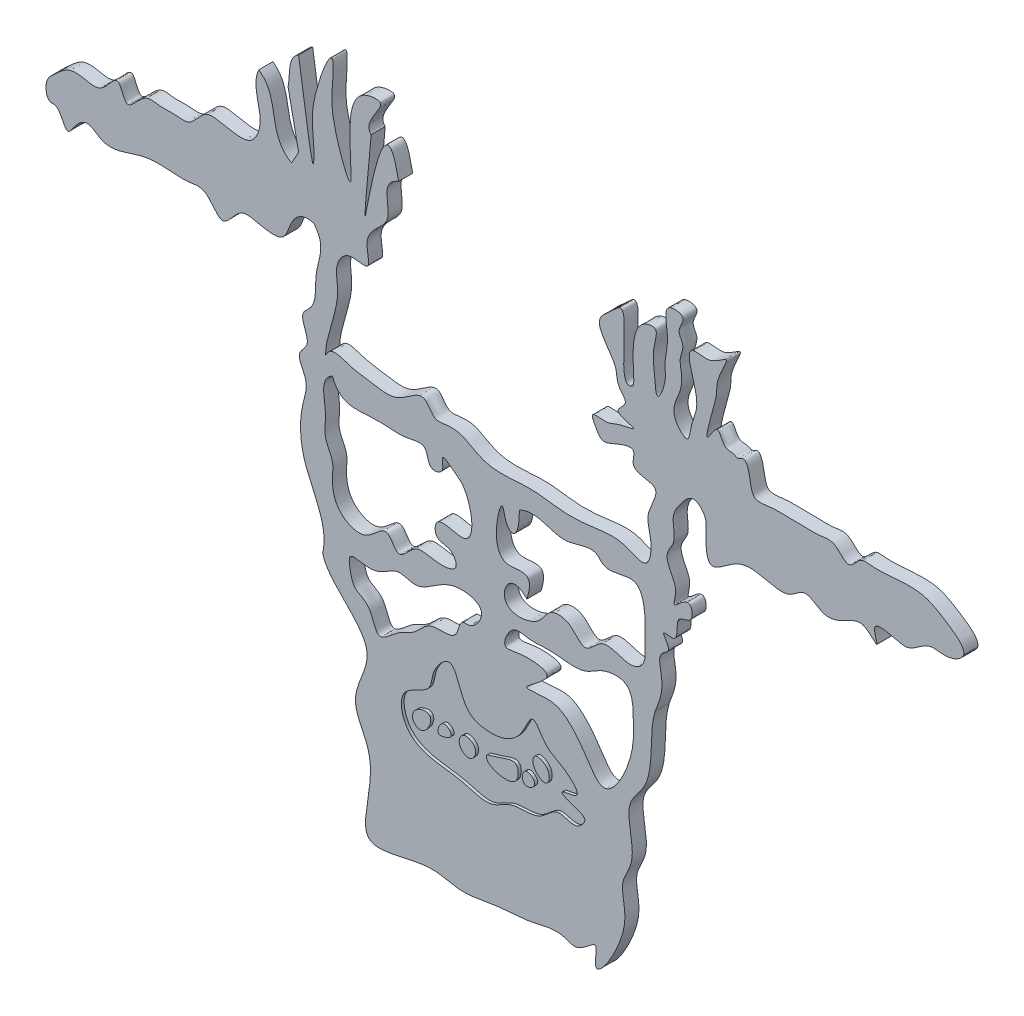
SolidWorks part; units mm, degrees
ref_plane "Plan de face" through (0, 0, 0) normal (0, 0, 1) x (1, 0, 0)
ref_plane "Plan de dessus" through (0, 0, 0) normal (0, 1, 0) x (1, 0, 0)
ref_plane "Plan de droite" through (0, 0, 0) normal (1, 0, 0) x (0, 0, -1)
sketch "Esquisse5" plane through (0, 0, 0) normal (0, 0, 1) x (1, 0, 0)
  spline S0 degree 3 poles (-109.3445, 25.1534) (-107.5893, 29.4219) (-101.3392, 25.9029) (-92.6956, 25.3142) (-83.4645, 22.6763) (-74.413, 33.2755) (-71.2749, 24.7007) (-66.4529, 25.3335) (-60.8204, 25.8472) (-54.3045, 20.5029) (-45.153, 19.8653) (-34.9131, 21.2066) (-24.0216, 18.622) (-12.6516, 20.1709) (-3.8665, 21.2156) (5.3646, 15.6477) (7.1198, 26.6974) (3.2173, 33.4052) (11.7792, 45.093) (-1.969, 43.5994) (1.4376, 52.0963) (-6.02, 50.089) (-11.0528, 46.8236) (-13.4058, 51.1132) (-15.6993, 55.6454) (-8.9166, 53.9478) (-5.9802, 56.3886) (4.108, 57.5122) (-8.7508, 59.2174) (-0.962, 63.8466) (-6.0647, 67.643) (-5.6768, 73.3095) (-9.5713, 78.0773) (-13.8345, 85.1581) (-8.5077, 88.8259) (0.4502, 98.2004) (-6.9651, 65.1054) (0, 70.636) knots 0 0 0 0 0.038716 0.066818 0.105889 0.146717 0.169739 0.177879 0.20067 0.234895 0.269429 0.30528 0.355982 0.398433 0.437537 0.464385 0.493232 0.529195 0.564337 0.596403 0.612682 0.632285 0.657558 0.673837 0.684133 0.703736 0.721045 0.742877 0.766185 0.783794 0.800555 0.820691 0.846941 0.873241 0.900963 0.913678 1 1 1 1
  spline S1 degree 3 poles (0, 70.636) (0.8053, 74.1338) (-3.1075, 91.5186) (8.9993, 92.506) (6.4299, 84.3585) (7.424, 80.3323) (8.0477, 68.4861) (11.9386, 77.7085) (10.6243, 83.9209) (13.2943, 91.2366) (9.6941, 102.3641) (19.6931, 100.9769) (14.8522, 95.7025) (18.5565, 91.734) (15.9877, 87.3637) (17.3791, 82.5577) (16.9196, 75.8625) (11.9734, 69.6035) (19.5998, 61.6604) (20.5501, 70.6781) (25.1421, 76.9754) (16.8283, 92.3811) (24.2143, 92.0829) (27.8296, 91.1829) (35.8211, 98.2302) (29.3274, 88.1257) (29.7364, 82.4119) (28.1594, 77.4041) (24.3037, 62.9473) (30.2481, 74.9158) (31.4808, 68.5753) (33.9084, 67.3915) (35.4935, 67.7493) (37.0636, 66.3876) (39.8623, 69.0192) (41.6497, 62.3983) (42.1041, 56.2374) (49.6882, 58.0085) (55.4741, 57.4372) (61.145, 57.6949) (66.2026, 57.3374) (71.7205, 59.0931) (76.5046, 50.82) (80.002, 58.066) (85.2929, 57.3078) (92.1595, 57.5578) (102.1598, 58.778) (110.3187, 54.2176) (120.723, 47.0205) (111.4915, 41.8788) (104.4068, 44.6031) (98.8248, 37.9068) (92.5887, 39.2631) (83.4924, 41.6725) (88.1798, 31.3671) (82.2057, 38.9151) (75.7762, 36.6539) (68.6206, 31.605) (61.0853, 39.3937) (55.3505, 32.6841) (46.6559, 34.4895) (37.2691, 36.8871) (25.9593, 24.6172) (25.5554, 37.3297) (26.158, 43.1802) (21.1466, 48.0577) (16.562, 42.6011) (12.9148, 37.0996) (15.6812, 30.0513) (10.4935, 24.536) (13.9024, 18.9519) (15.4944, 14.849) (13.2213, 7.817) (20.25, 16.8547) (21.7448, 7.3304) (13.6535, 8.3206) (17.1663, -1.6092) (8.5371, 1.2339) (14.2305, -4.4779) (8.0837, -7.0098) (11.3423, -16.1767) (9.4066, -21.6006) (7.7197, -25.6917) knots 0 0 0 0 0.045125 0.049215 0.059033 0.077849 0.089591 0.101354 0.11284 0.130913 0.149078 0.157421 0.167541 0.174531 0.184484 0.192706 0.203372 0.223278 0.234285 0.242046 0.262102 0.290783 0.294055 0.302236 0.314316 0.330881 0.339103 0.350018 0.368971 0.378972 0.388474 0.390275 0.394745 0.397177 0.400956 0.411147 0.422653 0.434106 0.447196 0.459468 0.466831 0.477466 0.490402 0.502673 0.506764 0.520672 0.544397 0.561597 0.5813 0.593788 0.606878 0.623723 0.633575 0.647507 0.656654 0.667781 0.676003 0.696456 0.711497 0.722862 0.738406 0.759677 0.780901 0.799195 0.808231 0.818403 0.829191 0.841996 0.85754 0.866687 0.881184 0.888727 0.896135 0.907501 0.916647 0.925794 0.939899 0.946444 0.955636 0.961421 0.97617 1 1 1 1
  spline S2 degree 3 poles (7.7197, -25.6917) (5.86, -31.6938) (7.081, -40.4964) (4.1065, -51.8144) (-2.5229, -57.9761) (-0.9213, -67.6544) (0.3405, -76.191) (-6.0452, -85.948) (1.4123, -96.2082) (-15.6555, -122.9421) (-12.0341, -104.6237) (-19.2372, -113.8384) (-26.9783, -109.4812) (-35.9985, -113.1217) (-48.753, -113.0684) (-60.3803, -116.5393) (-75.2312, -111.4227) (-96.823, -122.2835) (-94.0713, -101.5301) (-91.8687, -89.1125) (-102.2594, -74.62) (-86.759, -54.7603) (-108.1357, -44.5783) (-110.3558, -36.0857) knots 0 0 0 0 0.069204 0.098549 0.128834 0.163224 0.200739 0.224549 0.282385 0.351324 0.371645 0.400341 0.416282 0.464966 0.499497 0.562335 0.592403 0.681558 0.715947 0.784726 0.829733 0.894184 1 1 1 1
  spline S3 degree 3 poles (-110.3558, -36.0857) (-108.0423, -26.3601) (-118.3266, -14.2726) (-118.7144, 3.6631) (-114.8605, 14.2325) (-120.5579, 20.8624) (-113.3368, 26.0818) (-119.7152, 33.3225) (-111.9733, 38.7318) (-114.3277, 50.5388) (-108.8733, 58.305) (-113.5021, 63.8189) knots 0 0 0 0 0.256249 0.424787 0.497442 0.568529 0.611922 0.700995 0.737981 0.848138 1 1 1 1
  spline S4 degree 3 poles (-113.5021, 63.8189) (-117.2169, 64.9742) (-121.7481, 61.6652) (-123.7192, 51.4764) (-132.7312, 54.0058) (-140.6598, 55.2619) (-145.9399, 43.7999) (-151.1861, 56.0157) (-157.6195, 54.0793) (-164.3136, 54.3377) (-172.456, 55.2282) (-180.8309, 51.617) (-188.4989, 50.4972) (-193.4763, 55.5367) (-197.9973, 52.3988) (-201.64, 45.1731) (-203.3779, 54.6671) (-208.498, 53.929) (-209.2844, 60.5865) (-204.9438, 64.0796) (-200.8354, 68.1395) (-194.8236, 67.6944) (-188.3993, 65.5013) (-182.827, 76.7366) (-180.0769, 63.0752) (-174.2837, 74.1888) (-167.7841, 72.1256) (-163.064, 72.8538) (-156.393, 71.546) (-153.1821, 79.3156) (-144.5205, 78.1574) (-135.5079, 75.4657) (-130.4643, 88.4219) (-135.7655, 95.1484) (-133.0428, 101.2372) knots 0 0 0 0 0.042216 0.071541 0.118379 0.137114 0.178374 0.218206 0.244435 0.259423 0.310009 0.350927 0.382777 0.407913 0.429762 0.449677 0.484223 0.48797 0.515249 0.536611 0.566234 0.586842 0.614945 0.650934 0.676962 0.715948 0.73843 0.762786 0.781521 0.822781 0.84339 0.893975 0.924987 1 1 1 1
  spline S5 degree 3 poles (-133.0428, 101.2372) (-124.9979, 95.6095) (-130.5426, 83.8627) (-121.4015, 78.3705) knots 0 0 0 0 1 1 1 1
  spline S6 degree 1 poles (-121.4015, 78.3705) (-118.907, 82.9438) knots 0 0 1 1
  spline S7 degree 3 poles (-118.907, 112.8785) (-123.089, 110.3691) (-121.7421, 105.1701) (-122.6488, 101.2372) knots 0 0 0 0 1 1 1 1
  spline S8 degree 1 poles (-122.6488, 101.2372) (-118.907, 82.9438) knots 0 0 1 1
  spline S9 degree 3 poles (-118.907, 112.8785) (-117.987, 108.8644) (-113.4179, 71.5109) (-113.4509, 91.3381) (-115.6714, 99.2659) (-105.9463, 124.8116) (-106.9005, 108.6073) (-107.7487, 99.3774) (-97.8361, 72.1229) (-102.3522, 100.9727) (-98.2312, 112.8578) (-85.4927, 113.5021) (-96.5783, 104.4145) (-93.1299, 101.2372) knots 0 0 0 0 0.203682 0.231519 0.326163 0.443507 0.493613 0.55207 0.681472 0.803953 0.895137 0.917406 1 1 1 1
  spline S10 degree 3 poles (-93.1299, 101.2372) (-99.727, 29.6469) (-90.5137, 130.523) (-83.3772, 91.7419) knots 0 0 0 0 1 1 1 1
  spline S11 degree 3 poles (-83.3772, 91.7419) (-90.4487, 89.0332) (-82.1452, 76.719) (-97.4311, 71.2785) (-92.0615, 57.9547) (-101.9759, 61.8394) (-106.261, 54.7014) (-103.357, 42.6183) (-109.2901, 32.7752) (-109.3445, 25.1534) knots 0 0 0 0 0.182686 0.350003 0.446213 0.524078 0.620688 0.69561 1 1 1 1
  spline S12 degree 3 poles (-106.85, 20.1643) (-104.4176, 13.083) (-96.6637, 14.4454) (-87.0757, 14.4695) (-81.1053, 13.6737) (-72.7921, 16.7083) (-73.1953, 8.2187) (-64.4991, 10.4032) (-71.1458, 18.672) (-61.948, 11.0176) knots 0 0 0 0 0.292957 0.410083 0.535017 0.659951 0.764711 0.829986 1 1 1 1
  spline S13 degree 3 poles (-61.948, 11.0176) (-58.0095, 8.5158) (-53.229, -12.6527) (-70.4415, -2.7478) (-70.6719, -12.2414) (-64.6769, -11.3045) (-61.2675, -18.2118) (-70.8685, -19.2053) (-77.5919, -16.0195) (-83.4796, -25.9551) (-87.6215, -14.8363) (-93.5991, -24.0033) (-100.9517, -23.2409) (-106.4949, -18.4186) (-107.1233, -11.8842) (-106.311, -5.4546) (-110.3923, -0.1476) (-108.2057, 9.249) (-111.8764, 17.3936) (-106.85, 20.1643) knots 0 0 0 0 0.141144 0.214347 0.246175 0.28755 0.319673 0.374752 0.435224 0.489982 0.532801 0.596765 0.64313 0.691472 0.753 0.784828 0.837727 0.890242 1 1 1 1
  spline S14 degree 3 poles (-37.834, -13.9279) (-34.3708, -3.014) (-45.4498, -10.1611) (-50.0257, 0.0267) (-46.6057, 14.1179) (-45.1788, 2.9802) (-40.4947, 1.6382) (-40.4757, 12.1082) knots 0 0 0 0 0.291808 0.452467 0.680923 0.763866 1 1 1 1
  spline S15 degree 3 poles (-40.4757, 12.1082) (-33.8644, 15.4003) (-26.4482, 7.1618) (-14.3964, 14.5729) (-9.7666, 8.4806) (-4.6314, 10.551) (3.2143, 11.0146) (4.4297, 0.9831) (3.9653, -6.4701) (4.6546, -13.3829) (-2.5433, -17.4116) (-10.3977, -10.522) (-17.3152, -21.6724) (-22.1852, -12.6994) (-30.3709, -12.9154) (-33.4257, -20.9458) (-50.3798, -22.2502) (-43.8265, -7.8239) (-37.834, -13.9279) knots 0 0 0 0 0.130404 0.212458 0.225808 0.291887 0.310767 0.396955 0.445727 0.503148 0.528517 0.613998 0.668135 0.726665 0.773865 0.820643 0.908748 1 1 1 1
  spline S16 degree 3 poles (-69.4252, -24.9578) (-62.0643, -21.5416) (-51.0142, -24.6948) (-56.5213, -32.8682) (-61.8953, -31.9406) (-62.0215, -40.6856) (-72.4837, -37.0863) (-77.1682, -44.7125) (-83.8695, -46.3481) (-91.4744, -55.1585) (-92.7397, -43.4929) (-99.5179, -41.6386) (-100.504, -36.8842) (-101.5507, -30.5349) (-93.3049, -33.4359) (-88.393, -30.8721) (-83.1039, -27.5261) (-76.6527, -30.7738) (-69.4252, -24.9578) (-62.0643, -21.5416) (-51.0142, -24.6948) knots -0.207888 -0.158201 -0.084774 0 0.058602 0.128869 0.139409 0.186335 0.264119 0.327318 0.383463 0.450039 0.522701 0.565587 0.610699 0.642319 0.6935 0.757509 0.792112 0.841799 0.915226 1 1.058602 1.128869 1.139409 only from (-60.285, -22.6588) to (-60.285, -22.6588)
  spline S17 degree 3 poles (-38.966, -31.3288) (-47.5023, -33.6205) (-43.5055, -24.106) (-36.488, -26.3957) (-28.3257, -24.9207) (-18.3312, -27.6817) (-11.1552, -21.6964) (-0.2181, -20.6913) (0.0231, -33.8116) (0.2507, -44.399) (-9.4883, -63.9536) (-17.2987, -50.5788) (-22.3616, -44.2959) (-28.8973, -39.837) (-43.4581, -43.2274) (-24.101, -32.293) (-38.966, -31.3288) (-47.5023, -33.6205) (-43.5055, -24.106) knots -0.168834 -0.101482 -0.025755 0 0.049951 0.081412 0.138616 0.224421 0.269573 0.329636 0.398438 0.478824 0.5988 0.659915 0.726618 0.773963 0.831166 0.898518 0.974245 1 1.049951 1.081412 1.138616 only from (-45.3177, -32.3438) to (-45.3177, -32.3438)
  point P114 (-59.3851, 13.9625)
  point P229 (-86.534, 92.0905)
  point P252 (-105.3667, 54.2565)
  point P266 (-105.0789, 48.4359)
  point P271 (21.4038, 46.3571)
  point P275 (-118.907, 63.0945)
  point P285 (-98.7145, -41.0748)
  point P293 (5.8507, -43.9851)
  point P297 (6.4346, -34.3001)
  point P301 (-5.3523, 56.0203)
  point P305 (26.5556, 68.0611)
  point P309 (36.479, 78.3705)
  point P313 (35.6605, 70.3118)
  point P317 (29.8293, 71.9487)
  point P320 (32.6937, 68.0611)
  point P322 (35.7628, 67.345)
  point P323 (36.8882, 66.8335)
  point P324 (33.5122, 67.6519)
  point P325 (41.2872, 63.0945)
  point P326 (0, 0)
  point P327 (0, 70.636)
  point P328 (8.6131, 71.6798)
  point P329 (11.1183, 77.1076)
  point P330 (-67.7687, 13.0964)
  point P331 (-61.948, 11.0176)
  point P332 (-68.1523, 10.2504)
  point P333 (-46.329, 10.0491)
  point P334 (-40.4757, 12.1082)
  point P335 (-44.2652, 4.5292)
extrude "Boss.-Extru.1" add sketch "Esquisse5" along normal blind 2.5 and the other way blind 2.5
sketch "Esquisse10" plane through (0, 0, 2.5) normal (0, 0, 1) x (1, 0, 0)
  spline S0 degree 3 poles (-71.7082, -52.1571) (-62.9184, -42.3492) (-61.5257, -59.1414) (-50.0357, -62.4875) (-40.1173, -60.0504) (-35.9862, -46.6642) (-30.851, -57.3509) (-25.4724, -57.9903) (-16.7592, -66.6161) (-27.3959, -66.2868) (-21.5637, -69.6638) (-15.27, -70.2684) (-20.6675, -76.6957) (-27.2468, -71.8114) (-33.3059, -80.7937) (-42.9312, -78.2809) (-50.9315, -85.1058) (-60.4431, -81.072) (-70.4795, -80.4944) (-81.4537, -77.1571) (-84.2609, -62.3207) (-71.4637, -60.6586) (-71.7082, -52.1571) (-62.9184, -42.3492) (-61.5257, -59.1414) knots -0.133763 -0.074366 -0.043498 0 0.074169 0.111193 0.189975 0.228193 0.264295 0.316051 0.351334 0.380169 0.395456 0.431496 0.454031 0.49032 0.533246 0.593544 0.633375 0.691239 0.744913 0.806538 0.866237 0.925634 0.956502 1 1.074169 1.111193 1.189975 only from (-65.5402, -47.1818) to (-65.5402, -47.1818)
extrude "Enlèv. mat.-Extru.1" cut sketch "Esquisse10" against normal blind 1 and the other way blind 1
sketch "Esquisse11" plane through (0, 0, 2.5) normal (0, 0, 1) x (1, 0, 0)
  spline S0 degree 3 poles (-69.7666, -65.9105) (-76.9585, -66.3187) (-79.4724, -70.8228) (-74.178, -74.9917) (-69.7666, -65.9105) (-76.9585, -66.3187) (-79.4724, -70.8228) knots -0.761015 -0.577137 -0.213754 0 0.238985 0.422863 0.786246 1 1.238985 1.422863 1.786246 only from (-76.2453, -66.9696) to (-76.2453, -66.9696)
  spline S1 degree 3 poles (-70.3204, -71.4831) (-66.6909, -70.9588) (-63.1967, -69.4779) (-67.9341, -64.9138) (-70.3204, -71.4831) (-66.6909, -70.9588) (-63.1967, -69.4779) knots -0.7463 -0.476415 -0.134358 0 0.2537 0.523585 0.865642 1 1.2537 1.523585 1.865642 only from (-67.2683, -70.9732) to (-67.2683, -70.9732)
  spline S2 degree 3 poles (-54.5085, -68.5066) (-60.0647, -65.6897) (-61.9721, -68.8905) (-61.5328, -71.7372) (-57.5478, -74.4569) (-54.5085, -68.5066) (-60.0647, -65.6897) (-61.9721, -68.8905) knots -0.743381 -0.513618 -0.269206 0 0.150741 0.256619 0.486382 0.730794 1 1.150741 1.256619 1.486382 only from (-60.2382, -66.9696) to (-60.2382, -66.9696)
  spline S3 degree 3 poles (-51.971, -68.6884) (-52.18, -69.5554) (-51.7515, -71.7143) (-44.5977, -73.8375) (-40.61, -71.4537) (-40.7896, -64.0349) (-46.7055, -67.6471) (-51.971, -68.6884) (-52.18, -69.5554) (-51.7515, -71.7143) knots -0.403763 -0.096137 -0.009614 0 0.106462 0.312869 0.450858 0.596237 0.903863 0.990386 1 1.106462 1.312869 1.450858 only from (-52.0782, -69.1429) to (-52.0782, -69.1429)
  spline S4 degree 3 poles (-33.9967, -68.6088) (-39.0849, -65.0339) (-39.9252, -71.7265) (-36.0246, -71.4117) (-33.9967, -68.6088) (-39.0849, -65.0339) (-39.9252, -71.7265) knots -0.682913 -0.474338 -0.305258 0 0.317087 0.525662 0.694742 1 1.317087 1.525662 1.694742 only from (-38.1976, -66.9696) to (-38.1976, -66.9696)
  spline S5 degree 3 poles (-29.0663, -61.889) (-35.1019, -59.2154) (-36.2452, -64.6705) (-30.2317, -69.3241) (-29.0663, -61.889) (-35.1019, -59.2154) (-36.2452, -64.6705) knots -0.858516 -0.520227 -0.289645 0 0.141484 0.479773 0.710355 1 1.141484 1.479773 1.710355 only from (-34.9675, -60.7826) to (-34.9675, -60.7826)
  point P25 (-61.7336, -69.1429)
  point P27 (-61.4454, -70.9732)
  point P29 (-30.7498, -66.9696)
  point P30 (-49.6283, -68.1392)
  point P31 (-52.0782, -69.1429)
  point P32 (-51.3577, -70.9732)
  point P33 (0, 0)
extrude "Boss.-Extru.2" add sketch "Esquisse11" along normal blind 0.1 and the other way up to surface (5 mm away) separate body
